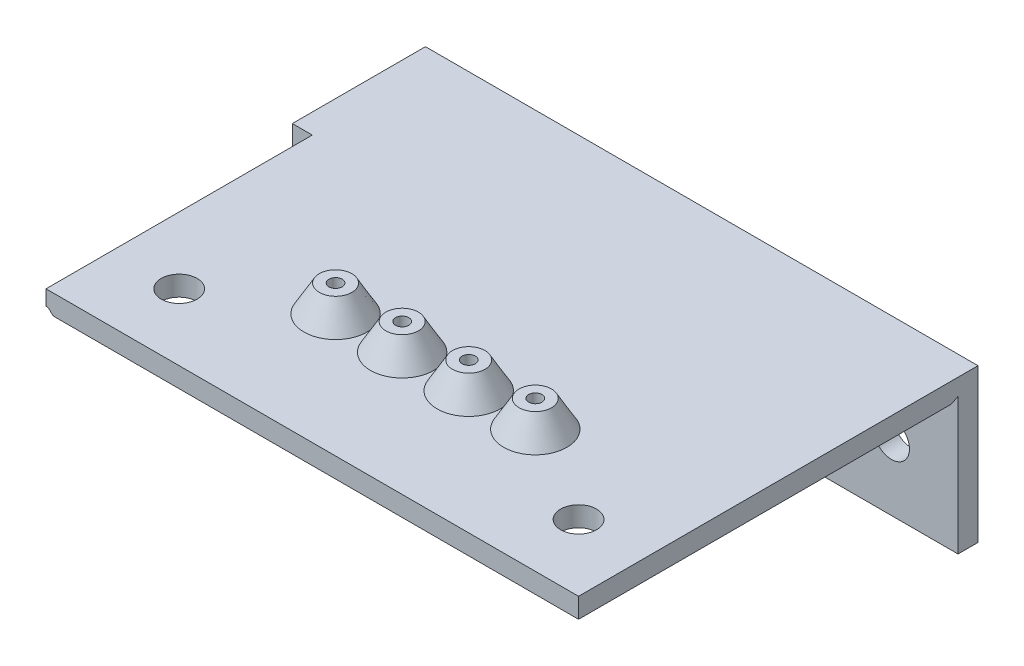
SolidWorks part; units mm, degrees
ref_plane "Front Plane" through (0, 0, 0) normal (0, 0, 1) x (1, 0, 0)
ref_plane "Top Plane" through (0, 0, 0) normal (0, 1, 0) x (1, 0, 0)
ref_plane "Right Plane" through (0, 0, 0) normal (1, 0, 0) x (0, 0, -1)
sketch "Sketch1" plane through (0, 0, 0) normal (0, 0, 1) x (1, 0, 0)
  line L0 (-40, -10) -> (-43, -10)
  line L1 (-40, -10) -> (40, -10)
  line L2 (-40, -10) -> (-40, 10)
  line L3 (-40, 10) -> (40, 10)
  line L4 (40, -10) -> (40, 10)
  line L5 (-40, -10) -> (40, 10) construction
  line L6 (-40, 10) -> (40, -10) construction
  line L7 (-43, -10) -> (-43, 13)
  line L8 (-43, 13) -> (40, 13)
  line L9 (40, 13) -> (40, 10)
  line L10 (-40, 0) -> (40, 0) construction
  circle A0 centre (-30, 0) radius 2.7
  circle A1 centre (-10, 0) radius 2.7
  circle A2 centre (10, 0) radius 2.7
  circle A3 centre (30, 0) radius 2.7
  point P0 (0, 0)
  dimension "D5" = 5.4
  dimension "D6" = 10
  dimension "D1" = 80
  dimension "D2" = 20
  dimension "D3" = 3
  dimension "D4" = 3
  dimension "D7" = 4
extrude "Boss-Extrude1" add sketch "Sketch1" along normal blind 3 contours L1 L4 L3 L2 region at (0, 0, 0)
extrude "Boss-Extrude2" add sketch "Sketch1<3>" along normal blind 20 contours L9 L8 L7 L0 L2 L3 region at (-41.5, -9.1387, 0)
sketch "Sketch1<3>" plane through (0, 0, 0) normal (0, 0, 1) x (1, 0, 0) same geometry as "Sketch1"
sketch "Sketch2" plane through (0, 0, 20) normal (0, 0, 1) x (1, 0, 0)
  line L1 (-40, 10) -> (40, 10)
  line L2 (-40, 10) -> (-40, 13)
  line L3 (-40, 13) -> (40, 13)
  line L4 (40, 10) -> (40, 13)
extrude "Boss-Extrude3" add sketch "Sketch2" along normal blind 40
sketch "Sketch3" plane through (0, 13, 0) normal (0, -1, 0) x (1, 0, 0)
  line L0 (0, 3) -> (0, 60) construction
  line L1 (-40, 3) -> (40, 3) construction
  line L2 (-40, 60) -> (40, 60) construction
  line L3 (-30, 3) -> (-30, 60) construction
  line L4 (-40, 60) -> (-40, 20) construction
  line L5 (40, 41.5) -> (-40, 41.5) construction
  line L6 (40, 60) -> (40, 3) construction
  circle A0 centre (-15, 41.5) radius 1
  circle A1 centre (5, 41.5) radius 1
  circle A2 centre (-30, 50) radius 2.7
  circle A3 centre (30, 50) radius 2.7
  circle A4 centre (15, 41.5) radius 1
  circle A5 centre (-5, 41.5) radius 1
  circle A6 centre (15, 41.5) radius 4.75
  circle A7 centre (5, 41.5) radius 4.75
  circle A8 centre (-5, 41.5) radius 4.75
  circle A9 centre (-15, 41.5) radius 4.75
  dimension "D1" = 2
  dimension "D2" = 2
  dimension "D4" = 5.4
  dimension "D5" = 10
  dimension "D7" = 25
  dimension "D9" = 9.5
  dimension "D3" = 10
  dimension "D6" = 38.5
  dimension "D8" = 45
extrude "Boss-Extrude5" add sketch "Sketch3" against normal blind 4 draft 30 contours A6 A4 | A4 | A7 A1 | A1 | A8 A5 | A5 | A9 A0 | A0 region at (-15, 13, 41.5) region at (5, 13, 41.5) region at (15, 13, 41.5) region at (-5, 13, 41.5) region at (10.3844, 13, 41.5) region at (0.3844, 13, 41.5) region at (-9.6156, 13, 41.5) region at (-19.6156, 13, 41.5)
extrude "Cut-Extrude2" cut sketch "Sketch3<6>" along normal up to surface and the other way up to surface contours A3 | A2 | A0 | A5 | A1 | A4 up to face at (-8, 10, 29.2) other way up to face at (-15, 17, 43.9406)
sketch "Sketch3<6>" plane through (0, 13, 0) normal (0, -1, 0) x (1, 0, 0) same geometry as "Sketch3"
sketch "Sketch4" plane through (0, 0, 3) normal (0, 0, 1) x (1, 0, 0)
  line L0 (-39.4697, 10.5303) -> (-39.0858, 10.1464)
  line L1 (-40, 10) -> (40, 10) construction
  line L2 (-40.5303, 9.4697) -> (-40.1464, 9.0858)
  line L3 (-40, -10) -> (-40, 10) construction
  line L4 (-40, 10) -> (40, 10) construction
  line L5 (-40, -10) -> (-40, 10) construction
  line L8 (-38.7322, 10) -> (-40, 8.7322)
  arc A0 (-39.4697, 10.5303) -> (-40.5303, 9.4697) centre (-40, 10) ccw
  arc A1 (-38.7322, 10) -> (-39.0858, 10.1464) centre (-38.7322, 10.5) cw
  arc A2 (-40, 8.7322) -> (-40.1464, 9.0858) centre (-40.5, 8.7322) ccw
  point P18 (-38.9393, 10)
  point P21 (-40, 8.9393)
  dimension "D1" = 1.5
  dimension "D4" = 0.5
  dimension "D2" = 135
  dimension "D3" = 135
extrude "Cut-Extrude3" cut sketch "Sketch4" along normal up to surface (57 mm away) contours A0 L2 A2 L8 A1 L0 up to face at (0, 11.5, 60)
sketch "Sketch5" plane through (0, -10, 0) normal (0, -1, 0) x (1, 0, 0)
  line L0 (-40, 3) -> (-40.5, 3)
  line L1 (-40.5, 3) -> (-40, 4)
  line L2 (-40, 20) -> (-40, 3) construction
  line L3 (-40, 4) -> (-40, 3)
  dimension "D1" = 0.5
  dimension "D2" = 1
extrude "Cut-Extrude4" cut sketch "Sketch5" against normal blind 20
sketch "Sketch6" plane through (40, 0, 0) normal (1, 0, 0) x (0, 0, -1)
  line L0 (-3, 10) -> (-3, 10.5)
  line L1 (-3, 10.5) -> (-4, 10)
  line L2 (-60, 10) -> (-3, 10) construction
  line L3 (-4, 10) -> (-3, 10)
  dimension "D1" = 0.5
  dimension "D2" = 1
extrude "Cut-Extrude5" cut sketch "Sketch6" against normal blind 80
